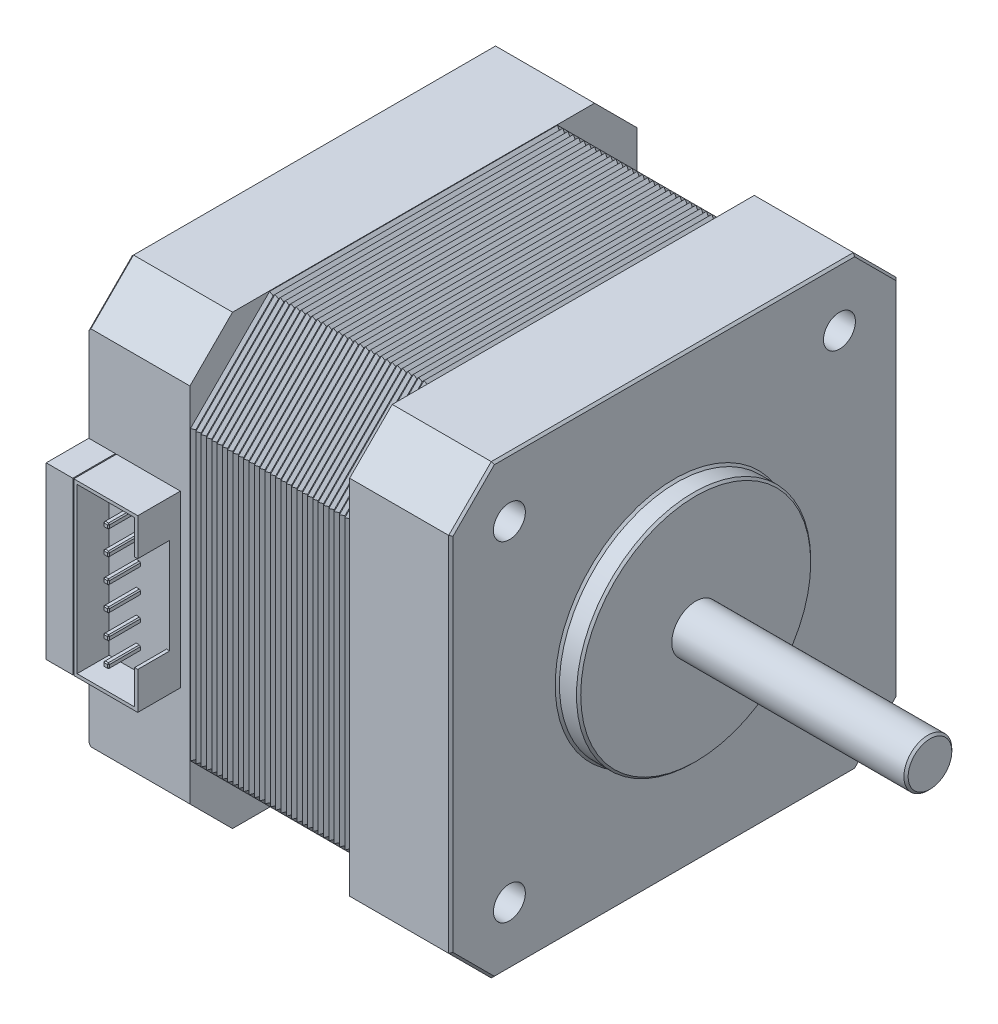
SolidWorks part; units mm, degrees
ref_plane "Front Plane" through (0, 0, 0) normal (0, 0, 1) x (1, 0, 0)
ref_plane "Top Plane" through (0, 0, 0) normal (0, 1, 0) x (1, 0, 0)
ref_plane "Right Plane" through (0, 0, 0) normal (1, 0, 0) x (0, 0, -1)
sketch "Sketch1" plane through (0, 0, 0) normal (1, 0, 0) x (0, 0, -1)
  line L1 (-21, 21) -> (21, 21)
  line L2 (-21, 21) -> (-21, -21)
  line L3 (-21, -21) -> (21, -21)
  line L4 (21, 21) -> (21, -21)
  line L5 (-21, 21) -> (21, -21) construction
  line L6 (-21, -21) -> (21, 21) construction
  point P0 (0, 0)
  dimension "D1" = 42
  dimension "D2" = 42
extrude "Boss-Extrude1" add sketch "Sketch1" along normal blind 9.5
chamfer "Chamfer1" distance 4 angle 45 4 edges at (4.75, -21, 21) (4.75, -21, -21) (4.75, 21, -21) (4.75, 21, 21)
sketch "Sketch2" plane through (9.5, 0, 0) normal (1, 0, 0) x (0, 0, -1)
  line L0 (-20.95, 13.5145) -> (-13.5145, 20.95)
  line L1 (-13.5145, 20.95) -> (13.5145, 20.95)
  line L2 (-20.95, 13.5145) -> (-20.95, -13.5145)
  line L3 (-13.5145, -20.95) -> (13.5145, -20.95)
  line L4 (20.95, 13.5145) -> (20.95, -13.5145)
  line L5 (-20.95, 20.95) -> (21, -21) construction
  line L6 (-21, -21) -> (21, 21) construction
  line L8 (-17, 21) -> (-21, 17) construction
  line L9 (0, 20.95) -> (0, -20.95) construction
  line L10 (13.5145, -20.95) -> (20.95, -13.5145)
  line L11 (20.95, 13.5145) -> (13.5145, 20.95)
  line L12 (-13.5145, -20.95) -> (-20.95, -13.5145)
  point P0 (0, 0)
  dimension "D1" = 41.9
  dimension "D3" = 2.5
extrude "Boss-Extrude2" add sketch "Sketch2" along normal blind 15
sketch "Sketch3" plane through (24.5, 0, 0) normal (1, 0, 0) x (0, 0, -1)
  line L0 (-21, 17) -> (-17, 21)
  line L1 (-17, -21) -> (17, -21)
  line L2 (-21, -17) -> (-21, 17)
  line L3 (-17, 21) -> (17, 21)
  line L4 (21, -17) -> (21, 17)
  line L5 (-21, -21) -> (21, 21) construction
  line L6 (-21, 21) -> (21, -21) construction
  line L7 (-21, -17) -> (-17, -21)
  line L8 (17, -21) -> (21, -17)
  line L9 (17, 21) -> (21, 17)
  point P0 (0, 0)
  dimension "D1" = 42
  dimension "D2" = 42
extrude "Boss-Extrude3" add sketch "Sketch3" along normal blind 9.5
sketch "Sketch4" plane through (34, 0, 0) normal (1, 0, 0) x (0, 0, -1)
  circle A0 centre (0, 0) radius 11
  dimension "D1" = 22
extrude "Boss-Extrude4" add sketch "Sketch4" along normal blind 2
sketch "Sketch5" plane through (36, 0, 0) normal (1, 0, 0) x (0, 0, -1)
  circle A0 centre (0, 0) radius 2.25
  dimension "D1" = 4.5
extrude "Boss-Extrude5" add sketch "Sketch5" along normal blind 22
sketch "Sketch6" plane through (34, 0, 0) normal (1, 0, 0) x (0, 0, -1)
  line L0 (0, 21) -> (0, -21) construction
  line L1 (17, 21) -> (-17, 21) construction
  line L2 (-17, -21) -> (17, -21) construction
  line L3 (-21, 0) -> (21, 0) construction
  line L4 (-21, 17) -> (-21, -17) construction
  line L5 (21, -17) -> (21, 17) construction
  circle A0 centre (-15.5, 15.5) radius 1.5
  circle A1 centre (15.5, 15.5) radius 1.5
  circle A2 centre (15.5, -15.5) radius 1.5
  circle A3 centre (-15.5, -15.5) radius 1.5
  dimension "D1" = 3
  dimension "D2" = 15.5
  dimension "D3" = 15.5
extrude "Cut-Extrude1" cut sketch "Sketch6" against normal blind 22
sketch "Sketch7" plane through (0, 0, 0) normal (-1, 0, 0) x (0, 0, 1)
  line L0 (0, 21) -> (0, -21) construction
  line L1 (-17, 21) -> (17, 21) construction
  line L2 (17, -21) -> (-17, -21) construction
  line L3 (-21, 0) -> (21, 0) construction
  line L4 (-21, -17) -> (-21, 17) construction
  line L5 (21, 17) -> (21, -17) construction
  circle A0 centre (-15.5, 15.5) radius 3
  circle A1 centre (15.5, 15.5) radius 3
  circle A2 centre (-15.5, -15.5) radius 3
  circle A3 centre (15.5, -15.5) radius 3
  dimension "D1" = 6
  dimension "D2" = 15.5
  dimension "D3" = 15.5
extrude "Cut-Extrude2" cut sketch "Sketch7" against normal blind 1
sketch "Sketch8" plane through (0, 0, 0) normal (-1, 0, 0) x (0, 0, 1)
  circle A0 centre (0, 0) radius 4.5
  dimension "D1" = 9
extrude "Cut-Extrude3" cut sketch "Sketch8" against normal blind 3
sketch "Sketch9" plane through (3, 0, 0) normal (-1, 0, 0) x (0, 0, 1)
  circle A0 centre (0, 0) radius 2.25
  dimension "D1" = 4.5
extrude "Boss-Extrude6" add sketch "Sketch9" along normal blind 2
sketch "Sketch10" plane through (3, 0, 0) normal (-1, 0, 0) x (0, 0, 1)
  circle A0 centre (0, 0) radius 3.5
  dimension "D1" = 7
extrude "Boss-Extrude7" add sketch "Sketch10" along normal blind 1
chamfer "Chamfer2" distance 0.2 angle 45 18 edges at (0, 19, -19) (0, 0, -21) (0, -19, -19) (0, -21, 0) (0, -19, 19) (0, 21, 0) (0, 19, 19) (34, 0, -21) (34, 19, -19) (34, -19, -19) (34, -21, 0) (34, -19, 19) (34, 0, 21) (34, 19, 19) (34, 21, 0) (36, 0, -11) (34, 0, -11) (58, 0, -2.25)
sketch "Sketch11" plane through (0, 0, 20.95) normal (0, 0, 1) x (1, 0, 0)
  line L0 (24.5, 20.95) -> (9.5, 20.95) construction
  line L1 (9.5, 21) -> (9.5, 17) construction
  line L2 (9.5, 20.95) -> (9.5, 13.5145) construction
  line L3 (9.5, 20.95) -> (9.738, 20.688)
  line L4 (9.738, 20.688) -> (10, 20.95)
  line L5 (24.5, 20.95) -> (9.5, 20.95) construction
  line L7 (10, 20.95) -> (9.5, 20.95)
  line L8 (0, 0) -> (33.8, 0) construction
  line L9 (33.8, -17) -> (33.8, 17) construction
  line L10 (9.738, -20.688) -> (10, -20.95)
  line L11 (10, -20.95) -> (9.5, -20.95)
  line L12 (9.5, -20.95) -> (9.738, -20.688)
  dimension "D1" = 45
  dimension "D2" = 47.747
  dimension "D3" = 0.5
extrude "Cut-Extrude4" cut sketch "Sketch11" against normal up to surface (41.9 mm away) up to face at (17, 0, -20.95)
pattern_linear "LPattern1" count 30 spacing 0.5 along (1, 0, 0) of "Cut-Extrude4"
sketch "Sketch13" plane through (0, -17.2322, 17.2322) normal (0, -0.7071, 0.7071) x (1, 0, 0)
  line L0 (33.8, 0) -> (0, 0) construction
  line L1 (33.8, -2.8284) -> (33.8, 2.8284) construction
  line L2 (9.5, -24.3701) -> (9.75, -24.1201)
  line L3 (9.75, -24.1201) -> (10, -24.3701)
  line L4 (10.5, -24.3701) -> (10.238, -24.3701) construction
  line L5 (10, -24.3701) -> (9.5, -24.3701)
  line L6 (9.75, 24.1201) -> (10, 24.3701)
  line L7 (10, 24.3701) -> (9.5, 24.3701)
  line L8 (9.5, 24.3701) -> (9.75, 24.1201)
  dimension "D1" = 45
  dimension "D2" = 45
  dimension "D3" = 0.5
extrude "Cut-Extrude6" cut sketch "Sketch13" against normal up to surface (48.7401 mm away) up to face at (16.9943, 20.5892, -13.8753)
pattern_linear "LPattern3" count 30 spacing 0.5 along (1, 0, 0) of "Cut-Extrude6"
sketch "Sketch14" plane through (0, -19, -19) normal (0, -0.7071, -0.7071) x (1, 0, 0)
  line L0 (0.2, 0) -> (33.8, 0) construction
  line L1 (0.2, 2.8284) -> (0.2, -2.8284) construction
  line L2 (33.8, -2.8284) -> (33.8, 2.8284) construction
  line L3 (24.5, 24.3701) -> (24.25, 24.1201)
  line L4 (24.25, 24.1201) -> (24, 24.3701)
  line L5 (24, 24.3701) -> (24.238, 24.3701) construction
  line L6 (24, 24.3701) -> (24.5, 24.3701)
  line L7 (24.25, -24.1201) -> (24, -24.3701)
  line L8 (24, -24.3701) -> (24.5, -24.3701)
  line L9 (24.5, -24.3701) -> (24.25, -24.1201)
  dimension "D1" = 45
  dimension "D2" = 45
  dimension "D3" = 0.5
extrude "Cut-Extrude7" cut sketch "Sketch14" against normal up to surface (53.7401 mm away) up to face at (4.85, 19, 19)
pattern_linear "LPattern4" count 30 spacing 0.5 along (-1, 0, 0) of "Cut-Extrude7"
sketch "Sketch15" plane through (0, 21, 0) normal (0, 1, 0) x (1, 0, 0)
  line L0 (24.5, 20.95) -> (24.25, 20.7)
  line L1 (24.25, 20.7) -> (24, 20.95)
  line L2 (24, 20.95) -> (24.25, 20.95) construction
  line L3 (24, 20.95) -> (24.5, 20.95)
  line L4 (0, 0) -> (33.8, 0) construction
  line L5 (33.8, -17) -> (33.8, 17) construction
  line L6 (24.25, -20.7) -> (24, -20.95)
  line L7 (24, -20.95) -> (24.5, -20.95)
  line L8 (24.5, -20.95) -> (24.25, -20.7)
  dimension "D1" = 45
  dimension "D2" = 45
  dimension "D3" = 0.5
extrude "Cut-Extrude8" cut sketch "Sketch15" against normal up to surface (42 mm away) up to face at (4.85, -21, 0)
pattern_linear "LPattern5" count 30 spacing 0.5 along (-1, 0, 0) of "Cut-Extrude8"
sketch "Sketch16" plane through (0, 0, 21) normal (0, 0, 1) x (1, 0, 0)
  line L0 (0, 0) -> (9.5, 0) construction
  line L1 (9.5, 13.5145) -> (9.5, -13.5145) construction
  line L2 (0, 8) -> (2.5, 8)
  line L3 (0, 16.7172) -> (0, -16.7172) construction
  line L4 (2.5, 8) -> (2.5, -8)
  line L5 (2.5, -8) -> (0, -8)
  line L6 (0, -8) -> (0, 8)
  dimension "D1" = 2.5
  dimension "D2" = 16
  dimension "D3" = 8
extrude "Boss-Extrude8" add sketch "Sketch16" along normal blind 4
sketch "Sketch17" plane through (0, 0, 21) normal (0, 0, 1) x (1, 0, 0)
  line L0 (2.5, -8) -> (2.5, 8) construction
  line L1 (2.6, -8) -> (8.6, -8)
  line L2 (2.6, -8) -> (2.6, 8)
  line L3 (2.6, 8) -> (8.6, 8)
  line L4 (8.6, -8) -> (8.6, -4.5)
  line L5 (2.6, -8) -> (8.6, 8) construction
  line L6 (2.6, 8) -> (8.6, -8) construction
  line L7 (8.6, 0) -> (2.6, 0) construction
  line L8 (8.3, 4.5) -> (8.3, 7.7)
  line L9 (2.9, 7.7) -> (8.3, 7.7)
  line L10 (8.6, 4.5) -> (8.6, 8)
  line L11 (2.9, -7.7) -> (2.9, 7.7)
  line L12 (2.9, -7.7) -> (8.3, -7.7)
  line L13 (8.3, -7.7) -> (8.3, -4.5)
  line L14 (8.3, -4.5) -> (8.6, -4.5)
  line L15 (8.3, 4.5) -> (8.6, 4.5)
  point P0 (5.6, 0)
  dimension "D1" = 16
  dimension "D2" = 0.1
  dimension "D3" = 6
  dimension "D4" = 9
  dimension "D5" = 3.5
  dimension "D6" = 0.3
extrude "Boss-Extrude9" add sketch "Sketch17" along normal blind 4
sketch "Sketch18" plane through (0, 0, 21) normal (0, 0, 1) x (1, 0, 0)
  line L0 (2.9, -7.7) -> (2.9, 7.7)
  line L1 (2.9, 7.7) -> (8.3, 7.7)
  line L2 (8.3, 7.7) -> (8.3, 4.5)
  line L3 (8.3, 4.5) -> (8.6, 4.5)
  line L4 (8.6, 4.5) -> (8.6, -4.5)
  line L5 (8.6, -4.5) -> (8.3, -4.5)
  line L6 (8.3, -4.5) -> (8.3, -7.7)
  line L7 (8.3, -7.7) -> (2.9, -7.7)
extrude "Boss-Extrude10" add sketch "Sketch18" along normal blind 1
sketch "Sketch19" plane through (0, 0, 22) normal (0, 0, 1) x (1, 0, 0)
  line L0 (5.6, -7.7) -> (5.6, 7.7) construction
  line L1 (2.9, -7.7) -> (8.3, -7.7) construction
  line L2 (8.3, 7.7) -> (2.9, 7.7) construction
  line L3 (2.9, 0) -> (8.6, 0) construction
  line L4 (2.9, 7.7) -> (2.9, -7.7) construction
  line L5 (8.6, -4.5) -> (8.6, 4.5) construction
  line L6 (5.85, 5.43) -> (5.35, 5.43)
  line L7 (5.85, -5.93) -> (5.35, -5.93)
  line L8 (5.85, -5.93) -> (5.85, -5.43)
  line L9 (5.85, -5.43) -> (5.35, -5.43)
  line L10 (5.35, -5.93) -> (5.35, -5.43)
  line L11 (5.85, -5.93) -> (5.35, -5.43) construction
  line L12 (5.85, -5.43) -> (5.35, -5.93) construction
  line L13 (5.85, -3.66) -> (5.35, -3.66)
  line L14 (5.85, -3.66) -> (5.85, -3.16)
  line L15 (5.85, -3.16) -> (5.35, -3.16)
  line L16 (5.35, -3.66) -> (5.35, -3.16)
  line L17 (5.85, -3.66) -> (5.35, -3.16) construction
  line L18 (5.85, -3.16) -> (5.35, -3.66) construction
  line L19 (5.85, -1.39) -> (5.35, -1.39)
  line L20 (5.85, -1.39) -> (5.85, -0.89)
  line L21 (5.85, -0.89) -> (5.35, -0.89)
  line L22 (5.35, -1.39) -> (5.35, -0.89)
  line L23 (5.85, -1.39) -> (5.35, -0.89) construction
  line L24 (5.85, -0.89) -> (5.35, -1.39) construction
  line L25 (5.85, 5.93) -> (5.85, 5.43)
  line L26 (5.85, 5.93) -> (5.35, 5.43) construction
  line L27 (5.85, 5.43) -> (5.35, 5.93) construction
  line L28 (5.85, 5.93) -> (5.35, 5.93)
  line L29 (5.35, 5.93) -> (5.35, 5.43)
  line L30 (5.85, 3.66) -> (5.85, 3.16)
  line L31 (5.85, 3.66) -> (5.35, 3.66)
  line L32 (5.85, 3.16) -> (5.35, 3.66) construction
  line L33 (5.35, 3.66) -> (5.35, 3.16)
  line L34 (5.85, 3.66) -> (5.35, 3.16) construction
  line L35 (5.85, 3.16) -> (5.35, 3.16)
  line L36 (5.85, 1.39) -> (5.35, 0.89) construction
  line L37 (5.85, 0.89) -> (5.35, 1.39) construction
  line L38 (5.85, 1.39) -> (5.85, 0.89)
  line L39 (5.85, 1.39) -> (5.35, 1.39)
  line L40 (5.35, 1.39) -> (5.35, 0.89)
  line L41 (5.85, 0.89) -> (5.35, 0.89)
  point P12 (5.6, -5.68)
  point P17 (5.6, -3.41)
  point P22 (5.6, -1.14)
  dimension "D1" = 0.5
  dimension "D2" = 0.5
  dimension "D3" = 0.5
  dimension "D4" = 0.5
  dimension "D5" = 0.5
  dimension "D6" = 0.5
  dimension "D7" = 1.77
  dimension "D8" = 1.77
  dimension "D9" = 1.77
extrude "Boss-Extrude11" add sketch "Sketch19" along normal up to surface (3 mm away) up to face at (6.55, 0, 25)
chamfer "Chamfer3" distance 0.1 angle 45 48 edges at (5.85, 5.68, 25) (5.85, 5.93, 23.5) (5.6, 5.93, 25) (5.35, 5.93, 23.5) (5.35, 5.68, 25) (5.35, 5.43, 23.5) (5.6, 5.43, 25) (5.85, 5.43, 23.5) (5.6, 3.66, 25) (5.85, 3.66, 23.5) (5.85, 3.41, 25) (5.35, 3.66, 23.5) (5.35, 3.41, 25) (5.35, 3.16, 23.5) (5.6, 3.16, 25) (5.85, 3.16, 23.5) (5.6, 1.39, 25) (5.85, 1.39, 23.5) (5.85, 1.14, 25) (5.35, 1.39, 23.5) (5.35, 1.14, 25) (5.35, 0.89, 23.5) (5.6, 0.89, 25) (5.85, 0.89, 23.5) (5.35, -1.14, 25) (5.35, -0.89, 23.5) (5.6, -0.89, 25) (5.85, -0.89, 23.5) (5.85, -1.14, 25) (5.35, -1.39, 23.5) (5.6, -1.39, 25) (5.85, -1.39, 23.5) (5.35, -3.41, 25) (5.35, -3.16, 23.5) (5.6, -3.16, 25) (5.85, -3.16, 23.5) (5.85, -3.41, 25) (5.35, -3.66, 23.5) (5.6, -3.66, 25) (5.85, -3.66, 23.5) (5.35, -5.68, 25) (5.35, -5.43, 23.5) (5.6, -5.43, 25) (5.35, -5.93, 23.5) (5.6, -5.93, 25) (5.85, -5.93, 23.5) (5.85, -5.68, 25) (5.85, -5.43, 23.5)
